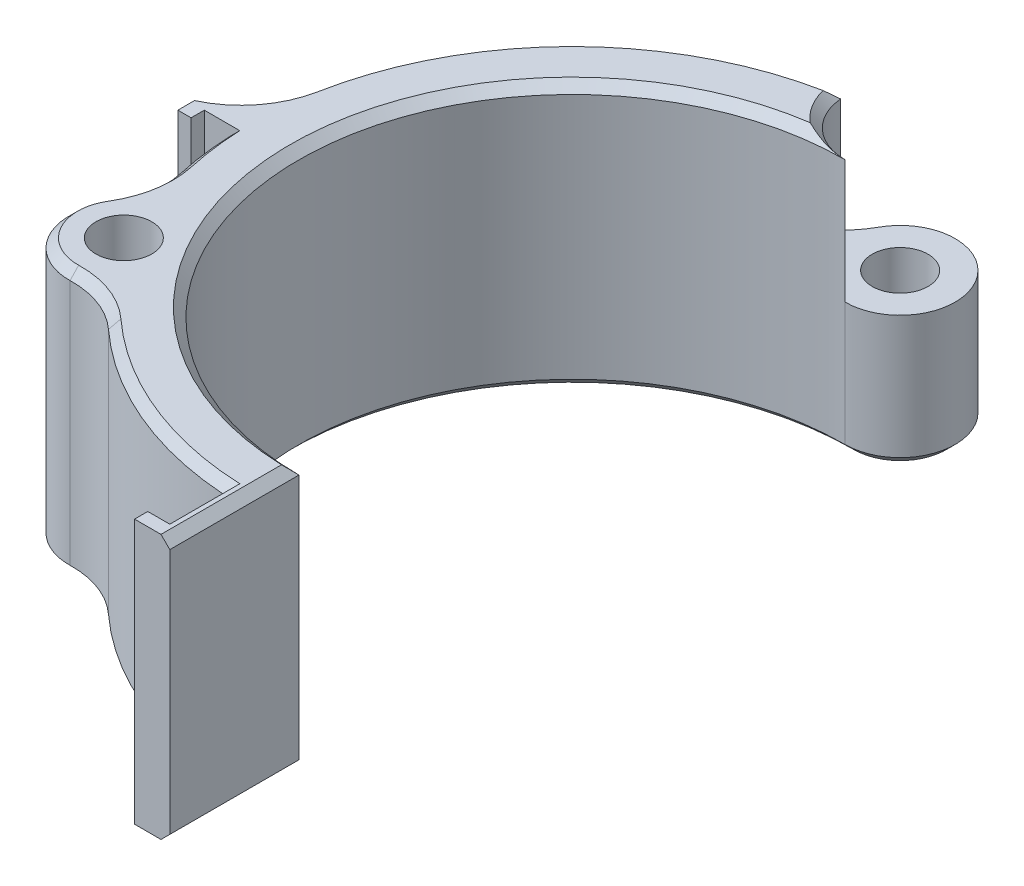
SolidWorks part; units mm, degrees
note: The reader was unsure of these and kept them because the rebuilt part matched: shared geometry of "Sketch3<6>".
ref_plane "Front Plane" through (0, 0, 0) normal (0, 0, 1) x (1, 0, 0)
ref_plane "Top Plane" through (0, 0, 0) normal (0, 1, 0) x (1, 0, 0)
ref_plane "Right Plane" through (0, 0, 0) normal (1, 0, 0) x (0, 0, -1)
sketch "Sketch3" plane through (0, 0, 0) normal (0, 1, 0) x (1, 0, 0)
  line L0 (0, 31) -> (0, 37.25)
  line L1 (0, -31) -> (0, -37.25)
  line L3 (0, -44.166) -> (-2.5, -44.166)
  line L6 (-37.25, 0) -> (-40.25, 0)
  line L7 (0, -44.166) -> (-4, -44.166)
  line L8 (0, -44.166) -> (0, -45.666)
  line L9 (0, -45.666) -> (-4, -45.666)
  line L10 (-2.5, -44.166) -> (0, -44.166)
  line L11 (-4, -44.166) -> (-4, -45.666)
  line L12 (-40.25, 0) -> (-40.25, -1.5)
  line L13 (-40.25, -1.5) -> (-37.2198, -1.5)
  line L14 (-37.2198, -1.5) -> (-37.25, 0)
  line L15 (-2.5, -44.166) -> (-2.5, -37.166)
  line L16 (-40.25, 0) -> (-41.75, 0)
  line L17 (-40.25, 0) -> (-40.25, -3)
  line L18 (-40.25, -3) -> (-41.75, -3)
  line L19 (-41.75, 0) -> (-41.75, -3)
  line L20 (-2.5, -30.899) -> (0, -31)
  line L21 (0, -44.166) -> (0, -31)
  line L22 (0, 0) -> (0, 50000) construction
  arc A0 (0, -31) -> (0, 31) centre (0, 0) cw
  arc A1 (0, -37.25) -> (0, 37.25) centre (0, 0) cw
  circle A2 centre (0, 37.25) radius 3.175
  circle A3 centre (0, 37.25) radius 6.25
  circle A4 centre (32.2594, -18.625) radius 3.175
  circle A5 centre (32.2594, -18.625) radius 6.25
  circle A6 centre (-32.2594, -18.625) radius 3.175
  circle A7 centre (-32.2594, -18.625) radius 6.25
  point P33 (0, 0)
  dimension "D1" = 31
  dimension "D5" = 12.5
  dimension "D6" = 6.35
  dimension "D4" = 2.5
  dimension "D7" = 1.5
  dimension "D8" = 4
  dimension "D9" = 1.5
  dimension "D10" = 3
  dimension "D11" = 3
  dimension "D12" = 1.5
  dimension "D3" = 7
  dimension "D13" = 3
extrude "Boss-Extrude2" add sketch "Sketch3" along normal blind 30 contours A7 A0 A3 A1 L14 | A1 A7 A6 | A1 A7 A6 | A1 A6 | A7 A1 L1 A0 | L21 A1 L15 L3 | L7 L11 L9 L8 L3 | L17 L16 L19 L18
extrude "Boss-Extrude3" add sketch "Sketch3<6>" along normal offset from surface (15 mm away) 15 contours L0 A3 A1 A2 | A1 A3 L0 A2 | L22 A2 L0 A3
sketch "Sketch3<6>" plane through (0, 0, 0) normal (0, 1, 0) x (1, 0, 0) same geometry as "Sketch3"
fillet "Fillet1" radius 10 4 edges at (-28.6914, 15, 23.7564) (-34.9193, 15, 12.9693) (-6.228, 7.5, -36.7257) (-37.25, 15, 0)
chamfer "Chamfer1" distance 1 angle 45 23 edges at (-2.5, 0, 40.666) (-2.5, 30, 40.666) (-14.6405, 0, 34.2523) (-14.6405, 30, 34.2523) (-28.3727, 30, 25.5075) (-28.3727, 0, 25.5075) (-37.6721, 0, 21.75) (-37.6721, 30, 21.75) (-36.942, 0, 4.7803) (-36.942, 30, 4.7803) (-36.2765, 30, 11.8177) (-36.2765, 0, 11.8177) (-38.3753, 30, -2.8982) (-38.3753, 0, -2.8982) (-27.8494, 0, -24.7381) (-7.9038, 0, -37.3252) (5.3762, 0, -40.4373) (0, 0, 38.333) (0, 30, 38.333) (-31, 0, 0) (-26.0706, 30, -26.6061) (-4.23, 30, -32.6489) (-31, 30, 0)
equation "\"Diameter\"= 62mm'Diameter of the outer surface of the body tube."
equation "\"Radius\"= \"Diameter\" / 2"
equation "\"D1@Sketch3\"=\"Radius\""
